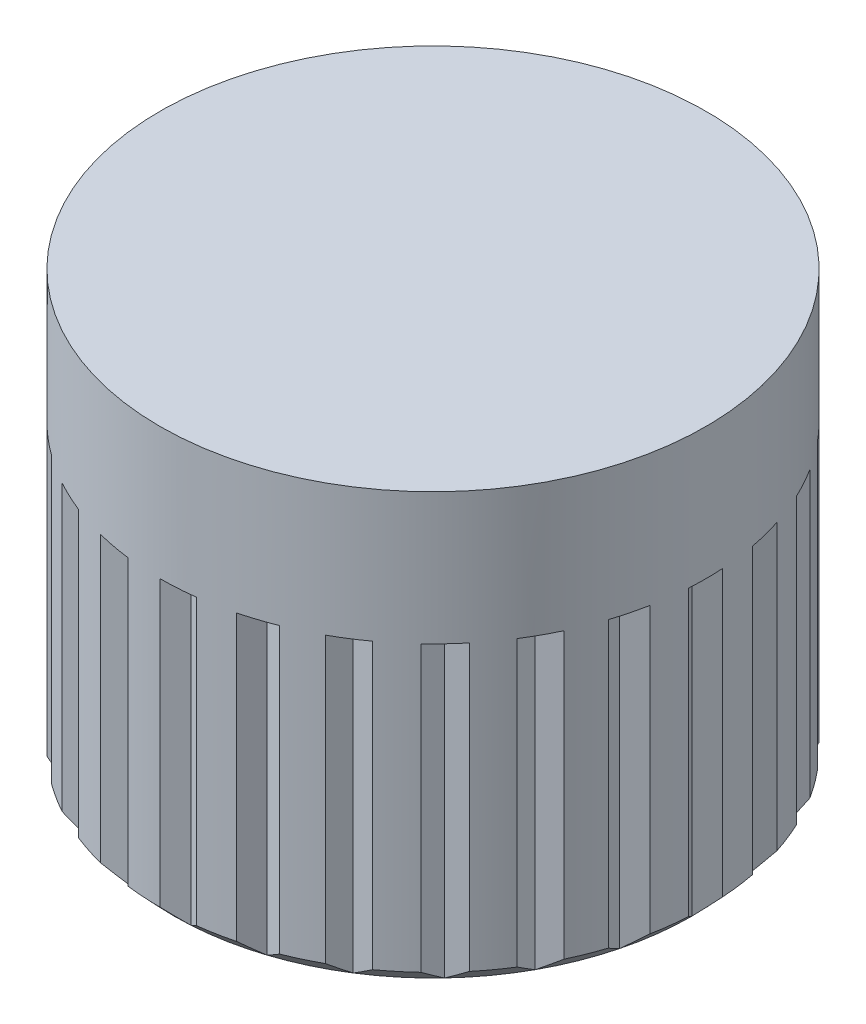
SolidWorks part; units mm, degrees
ref_plane "Front Plane" through (0, 0, 0) normal (0, 0, 1) x (1, 0, 0)
ref_plane "Top Plane" through (0, 0, 0) normal (0, 1, 0) x (1, 0, 0)
ref_plane "Right Plane" through (0, 0, 0) normal (1, 0, 0) x (0, 0, -1)
sketch "Sketch1" plane through (0, 0, 0) normal (0, 1, 0) x (1, 0, 0)
  line L0 (0, 0) -> (0, 2.9) construction
  line L3 (0.7212, 2.8089) -> (0.8498, 2.6154)
  line L4 (0, 2.9) -> (0.1727, 2.7446)
  line L5 (0.1727, 2.7446) -> (0.3635, 2.8771)
  line L6 (0.8498, 2.6154) -> (1.0676, 2.6964)
  line L7 (1.3971, 2.5413) -> (1.4735, 2.3219)
  line L8 (1.4735, 2.3219) -> (1.7046, 2.3461)
  line L9 (1.9852, 2.114) -> (2.0047, 1.8825)
  line L10 (2.0047, 1.8825) -> (2.2345, 1.8485)
  line L11 (2.4486, 1.5539) -> (2.4098, 1.3248)
  line L12 (2.4098, 1.3248) -> (2.624, 1.2348)
  line L13 (2.7581, 0.8961) -> (2.6636, 0.6839)
  line L14 (2.6636, 0.6839) -> (2.8486, 0.5434)
  line L15 (2.8943, 0.1821) -> (2.75, 0)
  line L16 (2.75, 0) -> (2.8943, -0.1821)
  line L17 (2.8486, -0.5434) -> (2.6636, -0.6839)
  line L18 (2.6636, -0.6839) -> (2.7581, -0.8961)
  line L19 (2.624, -1.2348) -> (2.4098, -1.3248)
  line L20 (2.4098, -1.3248) -> (2.4486, -1.5539)
  line L21 (2.2345, -1.8485) -> (2.0047, -1.8825)
  line L22 (2.0047, -1.8825) -> (1.9852, -2.114)
  line L23 (1.7046, -2.3461) -> (1.4735, -2.3219)
  line L24 (1.4735, -2.3219) -> (1.3971, -2.5413)
  line L25 (1.0676, -2.6964) -> (0.8498, -2.6154)
  line L26 (0.8498, -2.6154) -> (0.7212, -2.8089)
  line L27 (0.3635, -2.8771) -> (0.1727, -2.7446)
  line L28 (0.1727, -2.7446) -> (0, -2.9)
  line L29 (-0.3635, -2.8771) -> (-0.5153, -2.7013)
  line L30 (-0.5153, -2.7013) -> (-0.7212, -2.8089)
  line L31 (-1.0676, -2.6964) -> (-1.1709, -2.4883)
  line L32 (-1.1709, -2.4883) -> (-1.3971, -2.5413)
  line L33 (-1.7046, -2.3461) -> (-1.7529, -2.1189)
  line L34 (-1.7529, -2.1189) -> (-1.9852, -2.114)
  line L35 (-2.2345, -1.8485) -> (-2.2248, -1.6164)
  line L36 (-2.2248, -1.6164) -> (-2.4486, -1.5539)
  line L37 (-2.624, -1.2348) -> (-2.5569, -1.0123)
  line L38 (-2.5569, -1.0123) -> (-2.7581, -0.8961)
  line L39 (-2.8486, -0.5434) -> (-2.7283, -0.3447)
  line L40 (-2.7283, -0.3447) -> (-2.8943, -0.1821)
  line L41 (-2.8943, 0.1821) -> (-2.7283, 0.3447)
  line L42 (-2.7283, 0.3447) -> (-2.8486, 0.5434)
  line L43 (-2.7581, 0.8961) -> (-2.5569, 1.0123)
  line L44 (-2.5569, 1.0123) -> (-2.624, 1.2348)
  line L45 (-2.4486, 1.5539) -> (-2.2248, 1.6164)
  line L46 (-2.2248, 1.6164) -> (-2.2345, 1.8485)
  line L47 (-1.9852, 2.114) -> (-1.7529, 2.1189)
  line L48 (-1.7529, 2.1189) -> (-1.7046, 2.3461)
  line L49 (-1.3971, 2.5413) -> (-1.1709, 2.4883)
  line L50 (-1.1709, 2.4883) -> (-1.0676, 2.6964)
  line L51 (-0.7212, 2.8089) -> (-0.5153, 2.7013)
  line L52 (-0.5153, 2.7013) -> (-0.3635, 2.8771)
  circle A3 centre (0, 0) radius 2.75 construction
  arc A4 (0, 2.9) -> (-0.3635, 2.8771) centre (0, 0) ccw
  arc A5 (0.7212, 2.8089) -> (0.3635, 2.8771) centre (0, 0) ccw
  arc A6 (1.3971, 2.5413) -> (1.0676, 2.6964) centre (0, 0) ccw
  arc A7 (1.9852, 2.114) -> (1.7046, 2.3461) centre (0, 0) ccw
  arc A8 (2.4486, 1.5539) -> (2.2345, 1.8485) centre (0, 0) ccw
  arc A9 (2.7581, 0.8961) -> (2.624, 1.2348) centre (0, 0) ccw
  arc A10 (2.8943, 0.1821) -> (2.8486, 0.5434) centre (0, 0) ccw
  arc A11 (2.8486, -0.5434) -> (2.8943, -0.1821) centre (0, 0) ccw
  arc A12 (2.624, -1.2348) -> (2.7581, -0.8961) centre (0, 0) ccw
  arc A13 (2.2345, -1.8485) -> (2.4486, -1.5539) centre (0, 0) ccw
  arc A14 (1.7046, -2.3461) -> (1.9852, -2.114) centre (0, 0) ccw
  arc A15 (1.0676, -2.6964) -> (1.3971, -2.5413) centre (0, 0) ccw
  arc A16 (0.3635, -2.8771) -> (0.7212, -2.8089) centre (0, 0) ccw
  arc A17 (-0.3635, -2.8771) -> (0, -2.9) centre (0, 0) ccw
  arc A18 (-1.0676, -2.6964) -> (-0.7212, -2.8089) centre (0, 0) ccw
  arc A19 (-1.7046, -2.3461) -> (-1.3971, -2.5413) centre (0, 0) ccw
  arc A20 (-2.2345, -1.8485) -> (-1.9852, -2.114) centre (0, 0) ccw
  arc A21 (-2.624, -1.2348) -> (-2.4486, -1.5539) centre (0, 0) ccw
  arc A22 (-2.8486, -0.5434) -> (-2.7581, -0.8961) centre (0, 0) ccw
  arc A23 (-2.8943, 0.1821) -> (-2.8943, -0.1821) centre (0, 0) ccw
  arc A24 (-2.7581, 0.8961) -> (-2.8486, 0.5434) centre (0, 0) ccw
  arc A25 (-2.4486, 1.5539) -> (-2.624, 1.2348) centre (0, 0) ccw
  arc A26 (-1.9852, 2.114) -> (-2.2345, 1.8485) centre (0, 0) ccw
  arc A27 (-1.3971, 2.5413) -> (-1.7046, 2.3461) centre (0, 0) ccw
  arc A28 (-0.7212, 2.8089) -> (-1.0676, 2.6964) centre (0, 0) ccw
  circle A29 centre (0, 0) radius 1.25
  point P106 (0, 0)
  dimension "D1" = 25
  dimension "D2" = 5.5
  dimension "D3" = 2.5
extrude "Boss-Extrude1" add sketch "Sketch1" along normal blind 3.18
sketch "Sketch2" plane through (0, 0, 0) normal (1, 0, 0) x (0, 0, -1)
  line L0 (2.9, 0) -> (1.25, 0)
  line L1 (-1.25, 0) -> (-2.9, 0)
  line L2 (-2.75, 0) -> (-2.9, 0)
  line L3 (0, 0) -> (0, 3.4034) construction
  line L6 (-2.75, 0) -> (-2.9, 0.1584)
  line L7 (-2.9, 3.18) -> (-2.9, 0) construction
  line L8 (-2.9, 0.1584) -> (-2.9, 0)
revolve "Cut-Revolve1" cut sketch "Sketch2" angle 360 about L3
thread "Thread1" pitch 0.3528 start angle 0, offset 1, length 0, pitch 0.3528, diameter 2.5
ref_plane "Plane1" through (1.25, -1, 0) normal (0, 0, 1) x (1, 0, 0)
sketch "Thread Profile1" plane through (1.25, -1, 0) normal (0, 0, 1) x (1, 0, 0)
  line L0 (0, 0) -> (0, 0.3528) construction
  line L1 (0, 0) -> (0.1909, 0.1102)
  line L2 (0.1909, 0.1102) -> (0.1909, 0.1543)
  line L3 (0.1909, 0.1543) -> (0, 0.2646)
  line L4 (0.1909, 0.1323) -> (0, 0.1323) construction
  line L11 (0, 0) -> (0, 0.2646)
  point P2 (0, 0)
  dimension "Pitch" = 0.3528
  dimension "Profile_Angle" = 60
  dimension "Profile_Land" = 0.0441
  dimension "Profile_Height" = 0.1909
sketch "Sketch6" plane through (0, 3.18, 0) normal (0, 1, 0) x (1, 0, 0)
  circle A0 centre (0, 0) radius 2.9
extrude "Boss-Extrude2" add sketch "Sketch6" along normal blind 1.4
